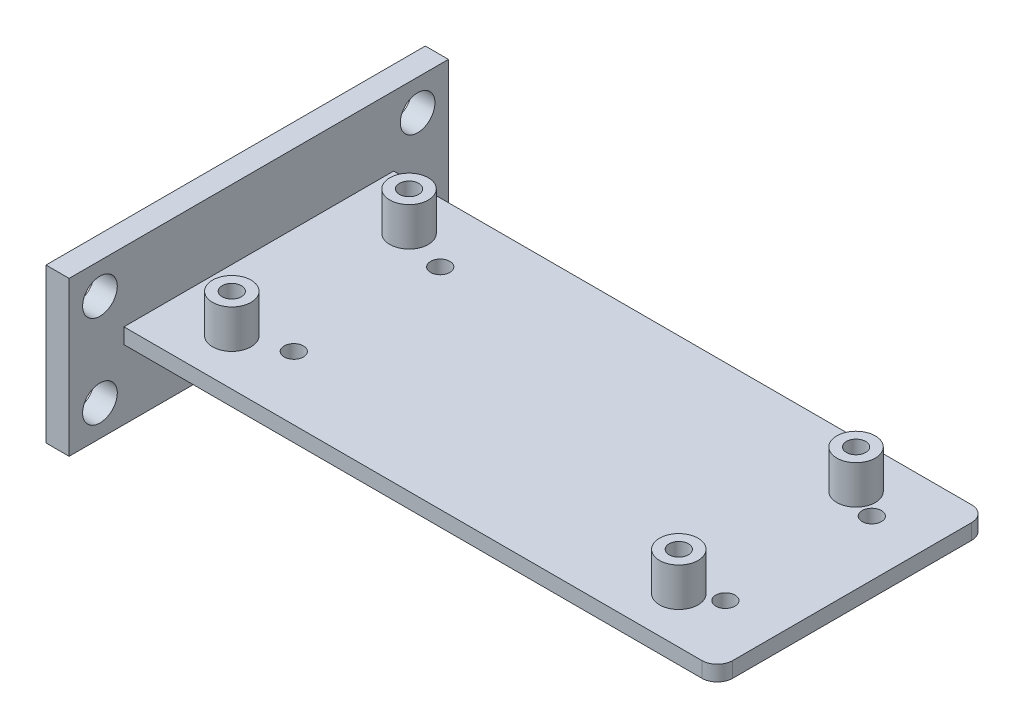
SolidWorks part; units mm, degrees
material "ABS"
ref_plane "Спереди" through (0, 0, 0) normal (0, 0, 1) x (1, 0, 0)
ref_plane "Сверху" through (0, 0, 0) normal (0, 1, 0) x (1, 0, 0)
ref_plane "Справа" through (0, 0, 0) normal (1, 0, 0) x (0, 0, -1)
sketch "Эскиз1" plane through (0, 0, 0) normal (0, 1, 0) x (1, 0, 0)
  line L1 (0, 0) -> (80, 0)
  line L2 (0, 0) -> (0, -35)
  line L3 (0, -35) -> (80, -35)
  line L4 (80, 0) -> (80, -35)
  dimension "D1" = 80
  dimension "D2" = 35
extrude "Бобышка-Вытянуть1" add sketch "Эскиз1" along normal blind 2
sketch "Эскиз2" plane through (0, 2, 0) normal (0, 1, 0) x (1, 0, 0)
  line L0 (0, 0) -> (0, -35) construction
  line L1 (80, -35) -> (80, 0) construction
  line L2 (80, 0) -> (0, 0) construction
  line L3 (0, -35) -> (80, -35) construction
  circle A0 centre (11, -6) radius 2.5
  circle A1 centre (11, -29) radius 2.5
  circle A2 centre (69, -6) radius 2.5
  circle A3 centre (69, -29) radius 2.5
  dimension "D1" = 11
  dimension "D2" = 11
  dimension "D3" = 11
  dimension "D4" = 11
  dimension "D5" = 6
  dimension "D6" = 6
  dimension "D7" = 5
  dimension "D8" = 6
  dimension "D9" = 6
  dimension "D10" = 5
  dimension "D11" = 5
  dimension "D12" = 5
extrude "Бобышка-Вытянуть2" add sketch "Эскиз2" along normal blind 5
sketch "Эскиз3" plane through (0, 7, 0) normal (0, 1, 0) x (1, 0, 0)
  circle A0 centre (11, -6) radius 1.25
  circle A1 centre (11, -29) radius 1.25
  circle A2 centre (69, -6) radius 1.25
  circle A3 centre (69, -29) radius 1.25
  dimension "D1" = 2.5
  dimension "D2" = 2.5
  dimension "D3" = 2.5
  dimension "D4" = 2.5
extrude "Вырез-Вытянуть1" cut sketch "Эскиз3" against normal through all both and the other way through all
sketch "Эскиз4" plane through (0, 2, 0) normal (0, 1, 0) x (1, 0, 0)
  line L0 (0, -17.5) -> (80, -17.5) construction
  line L1 (0, 0) -> (0, -35) construction
  line L2 (80, -35) -> (80, 0) construction
  circle A0 centre (4, -17.5) radius 2
  circle A1 centre (76, -17.5) radius 2
  dimension "D2" = 4
  dimension "D3" = 4
  dimension "D4" = 4
  dimension "D1" = 4
extrude "Вырез-Вытянуть2" [suppressed] cut sketch "Эскиз4" against normal through all
fillet "Скругление1" radius 2 1 edges at (0, 1, 0) type face fillet first side face at (0, 1, 17.5) second side face at (40, 1, 0)
fillet "Скругление2" radius 2 1 edges at (0, 1, 35) type face fillet first side face at (0, 1, 18.5) second side face at (40, 1, 35)
fillet "Скругление3" radius 2 1 edges at (80, 1, 35) type face fillet first side face at (41, 1, 35) second side face at (80, 1, 17.5)
fillet "Скругление4" radius 2 1 edges at (80, 1, 0) type face fillet first side face at (41, 1, 0) second side face at (80, 1, 16.5)
sketch "Эскиз5" plane through (0, 0, 0) normal (0, -1, 0) x (1, 0, 0)
  circle A0 centre (16.7893, 26.746) radius 1.25
  circle A1 centre (72.7893, 26.746) radius 1.25
  circle A2 centre (72.7893, 7.746) radius 1.25
  circle A3 centre (16.7893, 7.746) radius 1.25
  dimension "D1" = 2
  dimension "D2" = 2
extrude "Вырез-Вытянуть3" cut sketch "Эскиз5" against normal blind 10
sketch "Эскиз6" plane through (0, 0, 0) normal (0, -1, 0) x (1, 0, 0)
  circle A0 centre (16.7893, 26.746) radius 1.25
  circle A1 centre (16.7893, 26.746) radius 2.5
  circle A2 centre (72.7893, 26.746) radius 2.5
  circle A3 centre (72.7893, 26.746) radius 1.25
  circle A4 centre (72.7893, 7.746) radius 2.5
  circle A5 centre (72.7893, 7.746) radius 1.25
  circle A6 centre (16.7893, 7.746) radius 2.5
  circle A7 centre (16.7893, 7.746) radius 1.25
  dimension "D1" = 2
  dimension "D2" = 2
extrude "Бобышка-Вытянуть3" add sketch "Эскиз6" along normal blind 4
sketch "Эскиз7" plane through (0, 0, 0) normal (-1, 0, 0) x (0, 0, 1)
  line L0 (17.5, 2) -> (17.5, 0) construction
  line L1 (2, 2) -> (33, 2) construction
  line L2 (2, 0) -> (33, 0) construction
  line L3 (-7.1094, 1) -> (42.7824, 1) construction
  line L4 (42.1094, -9) -> (-7.1094, -9)
  line L5 (42.1094, -9) -> (42.1094, 11)
  line L6 (42.1094, 11) -> (-7.1094, 11)
  line L7 (-7.1094, -9) -> (-7.1094, 11)
  line L8 (42.1094, -9) -> (-7.1094, 11) construction
  line L9 (42.1094, 11) -> (-7.1094, -9) construction
  circle A0 centre (38.1094, -5) radius 2.25
  circle A1 centre (-3.1094, -5) radius 2.25
  circle A2 centre (-3.1094, 7) radius 2.25
  circle A3 centre (38.1094, 7) radius 2.25
  point P6 (17.5, 1)
  dimension "D1" = 4
  dimension "D2" = 4
  dimension "D3" = 20
extrude "Бобышка-Вытянуть4" add sketch "Эскиз7" against normal blind 3
